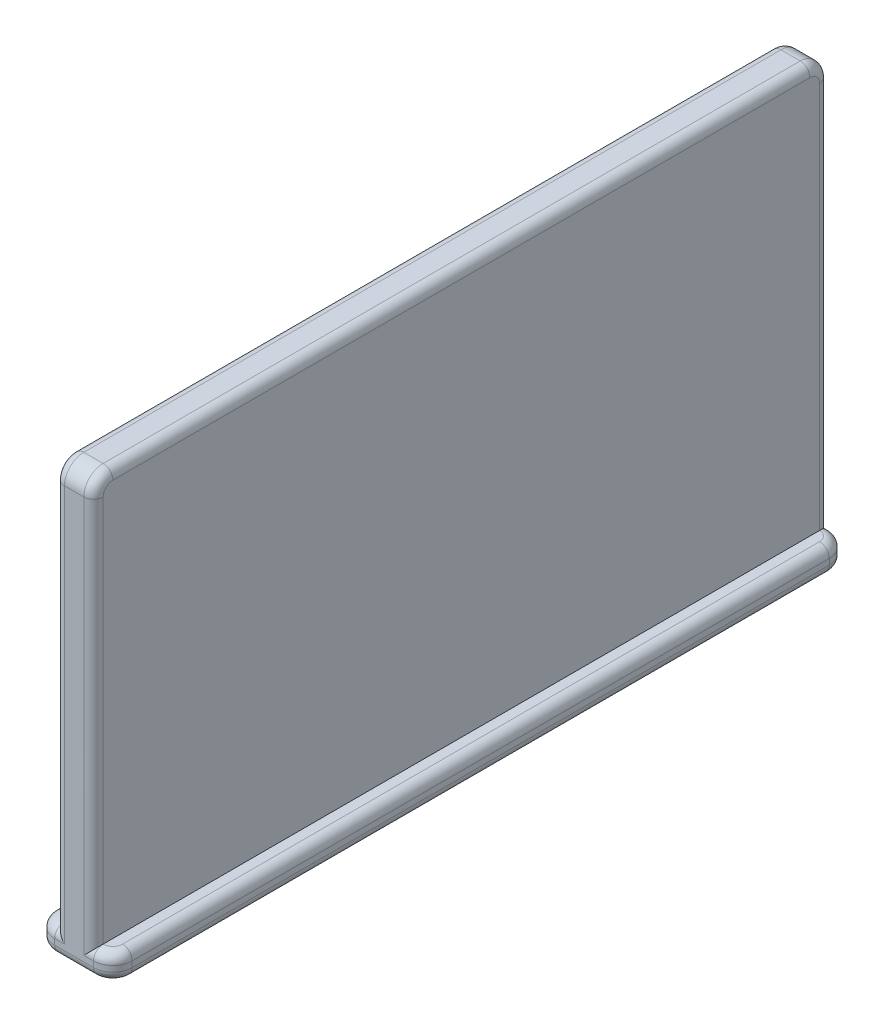
SolidWorks part; units mm, degrees
ref_plane "Front Plane" through (0, 0, 0) normal (0, 0, 1) x (1, 0, 0)
ref_plane "Top Plane" through (0, 0, 0) normal (0, 1, 0) x (1, 0, 0)
ref_plane "Right Plane" through (0, 0, 0) normal (1, 0, 0) x (0, 0, -1)
ref_plane "Plane1" through (-2, 0, 0) normal (-1, 0, 0) x (0, -1, 0)
sketch "Sketch1" plane through (-2, 0, 0) normal (-1, 0, 0) x (0, -1, 0)
  line L0 (0, 19) -> (-22.3, 19)
  line L1 (-22.3, 19) -> (-22.3, -19)
  line L2 (-22.3, -19) -> (0, -19)
  line L3 (0, -19) -> (0, 19)
extrude "Boss-Extrude1" add sketch "Sketch1" against normal blind 4
sketch "Sketch2" plane through (0, 0, 19) normal (0, 0, 1) x (1, 0, 0)
  line L0 (1, 1.3) -> (2, 1.3)
  line L1 (2, 1.3) -> (2, 22.3)
  line L2 (2, 22.3) -> (1, 22.3)
  line L3 (1, 22.3) -> (1, 1.3)
extrude "Cut-Extrude1" cut sketch "Sketch2" against normal through all
sketch "Sketch3" plane through (0, 0, 19) normal (0, 0, 1) x (1, 0, 0)
  line L0 (-2, 1.3) -> (-1, 1.3)
  line L1 (-1, 1.3) -> (-1, 22.3)
  line L2 (-1, 22.3) -> (-2, 22.3)
  line L3 (-2, 22.3) -> (-2, 1.3)
extrude "Cut-Extrude2" cut sketch "Sketch3" against normal through all
fillet "Fillet1" radius 1 6 edges at (-2, 0.65, 19) (0, 22.3, 19) (0, 22.3, -19) (2, 0.65, -19) (-2, 0.65, -19) (2, 0.65, 19) tangent propagation no
fillet "Fillet2" radius 0.5 24 edges at (-1.7071, 1.3, 18.7071) (-2, 1.3, 0) (-1.7071, 1.3, -18.7071) (-1, 11.3, -19) (-1, 22.0071, -18.7071) (-1, 22.3, 0) (-1, 22.0071, 18.7071) (-1, 11.3, 19) (1, 11.3, 19) (1, 22.0071, 18.7071) (1, 22.3, 0) (1, 22.0071, -18.7071) (1, 11.3, -19) (1.7071, 1.3, -18.7071) (2, 1.3, 0) (1.7071, 1.3, 18.7071) (2, 0, 0) (1.7071, 0, -18.7071) (1.7071, 0, 18.7071) (0, 0, -19) (0, 0, 19) (-1.7071, 0, -18.7071) (-1.7071, 0, 18.7071) (-2, 0, 0) tangent propagation no
